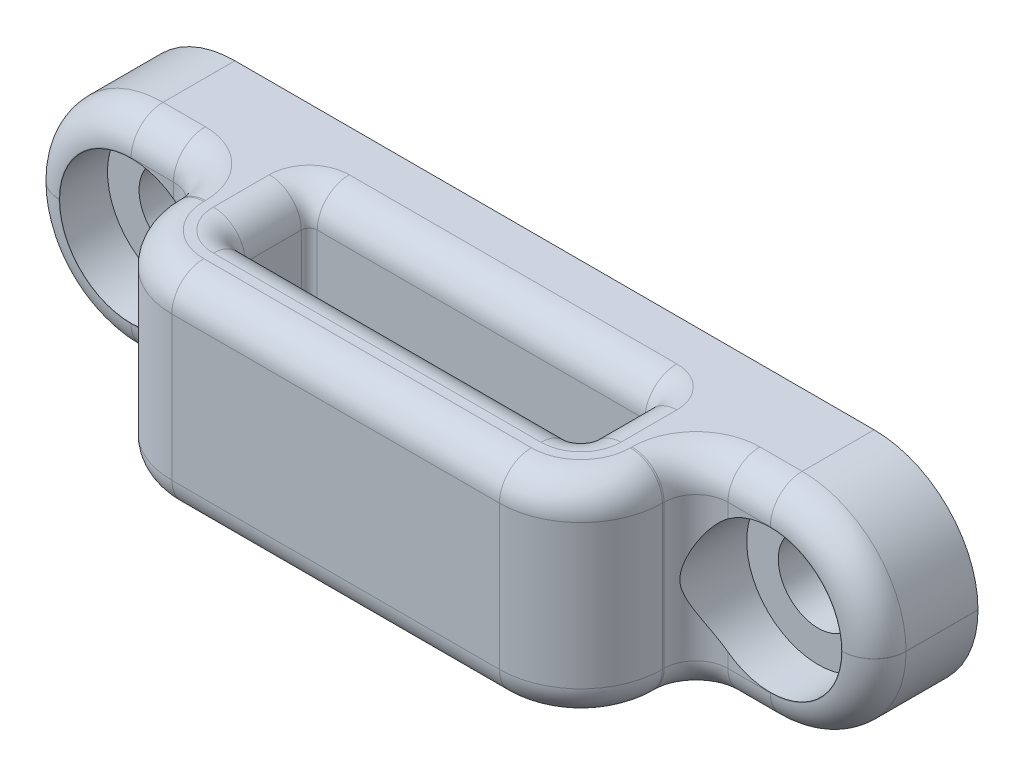
SolidWorks part; units mm, degrees
ref_plane "xy_plane" through (0, 0, 0) normal (0, 0, 1) x (1, 0, 0)
ref_plane "zx_plane" through (0, 0, 0) normal (0, 1, 0) x (1, 0, 0)
ref_plane "yz_plane" through (0, 0, 0) normal (1, 0, 0) x (0, 0, -1)
ref_axis "x_axis" through (-80.9, 0, 0) along (1, 0, 0)
ref_axis "y_axis" through (0, -50, 0) along (0, 1, 0)
ref_axis "z_axis" through (0, 0, -80.9) along (0, 0, 1)
ref_plane "yMid_plane" through (0, 0, 0) normal (0, 1, 0) x (1, 0, 0)
ref_plane "yMax_plane" through (0, 6.505, 0) normal (0, 1, 0) x (1, 0, 0)
ref_plane "yMin_plane" through (0, -6.505, 0) normal (0, 1, 0) x (1, 0, 0)
ref_plane "xMid_plane" through (0, 0, 0) normal (1, 0, 0) x (0, 0, -1)
ref_plane "xMax_plane" through (26.5, 0, 0) normal (1, 0, 0) x (0, 0, -1)
ref_plane "xMin_plane" through (-26.5, 0, 0) normal (1, 0, 0) x (0, 0, -1)
ref_plane "clampHoleTop_plane" through (0, 0, 3.5) normal (0, 0, 1) x (1, 0, 0)
ref_plane "screwHeadTopClearance_plane" through (0, 0, 6.5) normal (0, 0, 1) x (1, 0, 0)
sketch "strapSlot_sketch" plane through (0, 0, 0) normal (0, 1, 0) x (1, 0, 0)
  line L0 (-10.25, -9.1) -> (10.25, -9.1)
  line L1 (10.75, -8.6) -> (10.75, -5.1)
  line L2 (10.25, -4.6) -> (-10.25, -4.6)
  line L3 (-10.75, -5.1) -> (-10.75, -8.6)
  arc A0 (10.75, -5.1) -> (10.25, -4.6) centre (10.25, -5.1) ccw
  arc A1 (-10.25, -4.6) -> (-10.75, -5.1) centre (-10.25, -5.1) ccw
  arc A2 (-10.25, -9.1) -> (-10.75, -8.6) centre (-10.25, -8.6) cw
  arc A3 (10.25, -9.1) -> (10.75, -8.6) centre (10.25, -8.6) ccw
  point P3 (0, -4.6)
  point P8 (10.75, -4.6)
  point P11 (-10.75, -4.6)
  point P16 (10.75, -9.1)
  dimension "D2" = 0.5
  dimension "D3" = 21.5
  dimension "D4" = 4.5
  dimension "D1" = 4.6
sketch "strapSlotWalls_sketch" plane through (0, 0, 0) normal (0, 1, 0) x (1, 0, 0)
  line L14 (-10.25, -13.7) -> (10.25, -13.7)
  line L15 (-15.35, -5.1) -> (-15.35, -8.6)
  line L16 (10.25, 0) -> (-10.25, 0)
  line L17 (15.35, -8.6) -> (15.35, -5.1)
  line L18 (-10.25, -13.7) -> (10.25, -13.7)
  line L19 (-15.35, 0) -> (-15.35, -8.6)
  line L20 (15.35, 0) -> (-15.35, 0)
  line L21 (15.35, -8.6) -> (15.35, 0)
  arc A10 (-15.35, -8.6) -> (-10.25, -13.7) centre (-10.25, -8.6) ccw
  arc A11 (-10.25, 0) -> (-15.35, -5.1) centre (-10.25, -5.1) ccw
  arc A12 (15.35, -5.1) -> (10.25, 0) centre (10.25, -5.1) ccw
  arc A13 (10.25, -13.7) -> (15.35, -8.6) centre (10.25, -8.6) ccw
  arc A14 (-15.35, -8.6) -> (-10.25, -13.7) centre (-10.25, -8.6) ccw
  arc A17 (10.25, -13.7) -> (15.35, -8.6) centre (10.25, -8.6) ccw
  dimension "D1" = 4.6
sketch "mountHolePositions_sketch" plane through (0, 0, 0) normal (0, 0, 1) x (1, 0, 0)
  line L1 (-20, 0) -> (20, 0)
  line L2 (50, 0) -> (-50, 0) construction
  dimension "D1" = 40
sketch "mountingWings_sketch" plane through (0, 0, 0) normal (0, 0, 1) x (1, 0, 0)
  line L0 (55, -6.505) -> (-55, -6.505) construction
  line L1 (-20, -6.505) -> (20, -6.505)
  line L2 (-26.5, -0.005) -> (-26.5, 0.005)
  line L3 (-20, 6.505) -> (20, 6.505)
  line L4 (26.5, -0.005) -> (26.5, 0.005)
  line L5 (55, 6.505) -> (-55, 6.505) construction
  line L6 (-26.5, -55) -> (-26.5, 55) construction
  line L7 (26.5, -55) -> (26.5, 55) construction
  arc A0 (20, -6.505) -> (26.5, -0.005) centre (20, -0.005) ccw
  arc A1 (20, 6.505) -> (26.5, 0.005) centre (20, 0.005) cw
  arc A2 (-26.5, 0.005) -> (-20, 6.505) centre (-20, 0.005) cw
  arc A3 (-20, -6.505) -> (-26.5, -0.005) centre (-20, -0.005) cw
  dimension "D1" = 6.5
sketch "screwHeadClearanceHoles_sketch" plane through (0, 0, 0) normal (0, 0, 1) x (1, 0, 0)
  circle A0 centre (-20, 0) radius 4.475
  circle A1 centre (20, 0) radius 4.475
  dimension "D1" = 8.95
sketch "screwClearanceHoles_sketch" plane through (0, 0, 0) normal (0, 0, 1) x (1, 0, 0)
  circle A0 centre (-20, 0) radius 2.5
  circle A1 centre (20, 0) radius 2.5
  dimension "D1" = 5
extrude "strapSurroundingMeat_extrude" add sketch "strapSlotWalls_sketch" along normal up to surface (6.505 mm away) from surface up to plane "yMax_plane" starting at plane "yMin_plane"
extrude "mountingWings_extrude" add sketch "mountingWings_sketch" along normal blind 6.5 from surface starting at plane "xy_plane"
extrude "strapSlot_extrude" cut sketch "strapSlot_sketch" against normal through all both and the other way through all from surface starting at plane "yMid_plane"
fillet "slotBuglingFillet" radius 2 16 edges at (0, 6.505, 4.6) (-10.75, 6.505, 6.85) (0, 6.505, 9.1) (10.75, 6.505, 6.85) (-10.75, -6.505, 6.85) (0, -6.505, 4.6) (10.75, -6.505, 6.85) (0, -6.505, 9.1) (10.6036, 6.505, 4.7464) (-10.6036, 6.505, 4.7464) (-10.6036, 6.505, 8.9536) (10.6036, 6.505, 8.9536) (-10.6036, -6.505, 8.9536) (-10.6036, -6.505, 4.7464) (10.6036, -6.505, 4.7464) (10.6036, -6.505, 8.9536)
fillet "cosmeticFillet" radius 2 22 edges at (-15.35, -6.505, 7.55) (-13.8562, -6.505, 12.2062) (0, -6.505, 13.7) (13.8562, -6.505, 12.2062) (15.35, -6.505, 7.55) (-15.35, 6.505, 7.55) (-13.8562, 6.505, 12.2062) (0, 6.505, 13.7) (13.8562, 6.505, 12.2062) (15.35, 6.505, 7.55) (-17.675, -6.505, 6.5) (-24.5962, -4.6012, 6.5) (-26.5, 0, 6.5) (-24.5962, 4.6012, 6.5) (-17.675, 6.505, 6.5) (-15.35, 0, 6.5) (17.675, 6.505, 6.5) (24.5962, 4.6012, 6.5) (26.5, 0, 6.5) (24.5962, -4.6012, 6.5) (17.675, -6.505, 6.5) (15.35, 0, 6.5) tangent propagation no
extrude "screwClearanceHoles_cut" cut sketch "screwClearanceHoles_sketch" along normal through all
extrude "screwHeadClearanceHoles_cut" cut sketch "screwHeadClearanceHoles_sketch" along normal through all from surface starting at plane "clampHoleTop_plane"
equation "\"strapWidth\"= 20mm"
equation "\"strapThickness\"= 3.2mm"
equation "\"slotWidth\" = \"strapWidth\" + 2 * \"slotCornerRoundingFilletRadius\" + 2 * \"3dPrinterNoodleBulgeCompensation\""
equation "\"slotThickness\"= 4.5mm"
equation "\"D3@strapSlot_sketch\"=\"slotWidth\""
equation "\"D4@strapSlot_sketch\"=\"slotThickness\""
equation "\"extentY\"= 13.01mm"
equation "\"D1@yMax_plane\"=\"extentY\"/2"
equation "\"D1@yMin_plane\"=\"extentY\"/2"
equation "\"mountHolesIntervalX\"= ( fix ( \"minimumAllowedMountHolesIntervalX\" / \"mountHolesIntervalPreferredIncrement\" ) + iif ( fix ( \"minimumAllowedMountHolesIntervalX\" / \"mountHolesIntervalPreferredIncrement\" ) = ( \"minimumAllowedMountHolesIntervalX\" / \"mountHolesIntervalPreferredIncrement\" ) , 0 , 1 ) ) * \"mountHolesIntervalPreferredIncrement\""
equation "\"D1@mountHolePositions_sketch\"= \"mountHolesIntervalX\""
equation "\"D1@screwClearanceHoles_sketch\" = \"mountScrewClearanceDiameter\""
equation "\"D1@screwHeadClearanceHoles_sketch\" = \"mountScrewHeadClearanceDiameter\""
equation "\"strapSlotWallThickness\"= 4.6mm"
equation "\"D1@strapSlot_sketch\"=\"strapSlotWallThickness\""
equation "\"mountScrewClampingThickness\"= 3.5mm"
equation "\"mountScrewHeadClearanceThickness\"= 3mm"
equation "\"mountScrewClearanceDiameter\"= 4.50mm + 2 * \"3dPrinterNoodleBulgeCompensation\""
equation "\"mountScrewHeadClearanceDiameter\" = 8.45mm + 2 * \"3dPrinterNoodleBulgeCompensation\""
equation "\"mountScrewClampingDiameter\" = 13"
equation "\"D1@mountingWings_sketch\" = \"extentX\""
equation "\"extentX\"= \"mountHolesIntervalX\" + \"mountScrewClampingDiameter\""
equation "\"wingThickness\"= \"mountScrewClampingThickness\" + \"mountScrewHeadClearanceThickness\""
equation "\"D1@clampHoleTop_plane\"=\"mountScrewClampingThickness\""
equation "\"D1@screwHeadTopClearance_plane\"=\"mountScrewHeadClearanceThickness\""
equation "\"minimumAllowedMountHolesIntervalX\"= \"slotWidth\" + 2 * \"strapSlotWallThickness\" + \"mountScrewHeadClearanceDiameter\""
equation "\"mountHolesIntervalPreferredIncrement\"= 5mm"
equation "\"D1@strapSlotWalls_sketch\"=\"strapSlotWallThickness\""
equation "\"D2@strapSlot_sketch\" = \"slotCornerRoundingFilletRadius\""
equation "\"buglingFilletRadius\"= 2mm"
equation "\"D1@slotBuglingFillet\" = \"buglingFilletRadius\""
equation "\"slotCornerRoundingFilletRadius\"= 0.5mm"
equation "\"cosmeticFilletRadius\"= 2mm"
equation "\"D1@xMax_plane\"=\"extentX\"/2"
equation "\"D1@xMin_plane\"=\"extentX\"/2"
equation "\"D1@mountingWings_sketch\" = \"mountScrewClampingDiameter\" / 2"
equation "\"D1@mountingWings_extrude\" = \"wingThickness\""
equation "\"D1@cosmeticFillet\"=\"cosmeticFilletRadius\""
equation "\"3dPrinterNoodleBulgeCompensation\" = 0.25mm"
